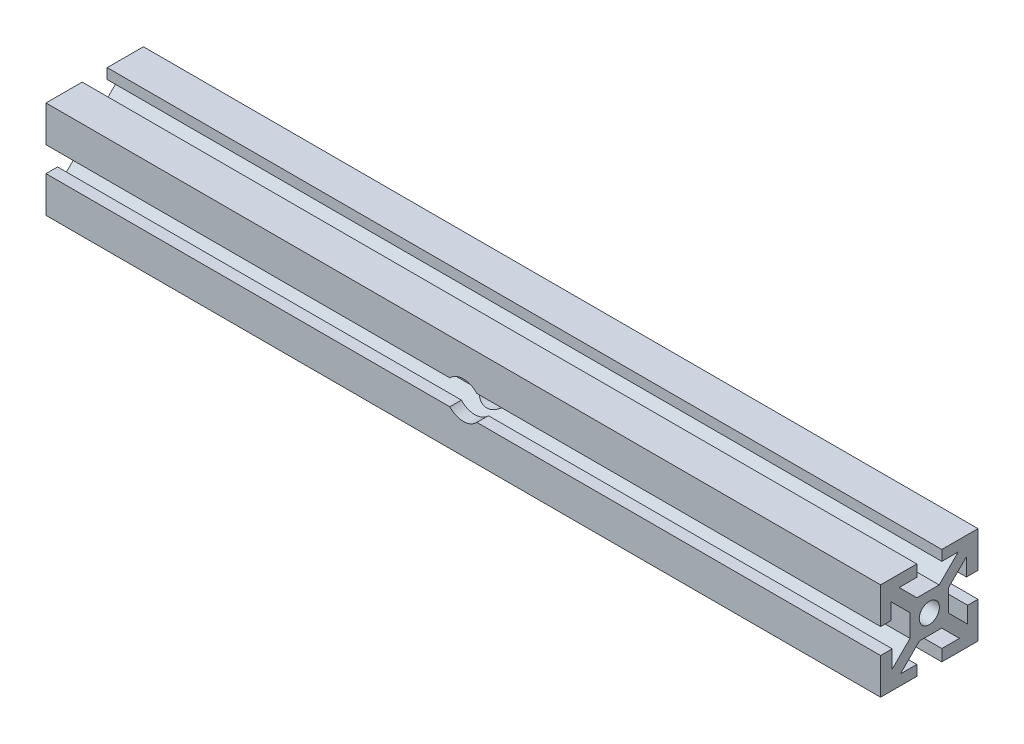
SolidWorks part; units mm, degrees
material "6061 Alloy"
ref_plane "Front Plane" through (0, 0, 0) normal (0, 0, 1) x (1, 0, 0)
ref_plane "Top Plane" through (0, 0, 0) normal (0, 1, 0) x (1, 0, 0)
ref_plane "Right Plane" through (0, 0, 0) normal (1, 0, 0) x (0, 0, -1)
sketch "Sketch1" plane through (0, 0, 0) normal (1, 0, 0) x (0, 0, -1)
  line L0 (2.5534, 5) -> (7.4749, 9.9215)
  line L1 (-5, 5) -> (5, 5)
  line L2 (-5, 5) -> (-5, -5)
  line L3 (-5, -5) -> (5, -5)
  line L4 (5, 5) -> (5, -5)
  line L5 (-5, 5) -> (5, -5) construction
  line L6 (-5, -5) -> (5, 5) construction
  line L7 (7.4749, 9.9215) -> (9.5962, 7.8001)
  line L8 (9.5962, 7.8001) -> (5, 3.2039)
  line L9 (5, 5) -> (13.6489, 13.6489) construction
  line L10 (7.4749, 9.9215) -> (3.24, 9.9215)
  line L11 (3.24, 9.9215) -> (3.24, 12.5962)
  line L12 (3.24, 12.5962) -> (12.5962, 12.5962)
  line L13 (9.5962, 7.8001) -> (9.5962, 3.24)
  line L14 (9.5962, 3.24) -> (12.5962, 3.24)
  line L15 (12.5962, 3.24) -> (12.5962, 12.5962)
  line L17 (0, 0) -> (0, 24.089) construction
  line L18 (0, 0) -> (23.75, 0) construction
  circle A0 centre (0, 0) radius 2.605
  point P0 (0, 0)
  dimension "D1" = 5.21
  dimension "D2" = 10
  dimension "D3" = 10
  dimension "D4" = 3
  dimension "D5" = 1.27
  dimension "D6" = 6.5
  dimension "D7" = 3.24
  dimension "D8" = 3.24
  dimension "D9" = 3
extrude "Boss-Extrude1" add sketch "Sketch1" along normal blind 215.9 contours L4 L1 L2 L3 A0 | L8 L7 L0 L1 L4 | L14 L15 L12 L11 L10 L7 L13 region at (0, 4.8586, -3.7767) region at (0, 6.7479, -6.3823) region at (0, 9.18, -9.3105)
ref_axis "Axis1" through (0, 0, 0) along (1, 0, 0)
pattern_circular "CirPattern1" count 4 over 360 about axis through (0, 0, 0) along (1, 0, 0) of "Boss-Extrude1"
sketch "Sketch2" plane through (0, 0, 12.5962) normal (0, 0, 1) x (1, 0, 0)
  line L0 (0, -9.5962) -> (0, -5) construction
  circle A0 centre (107.95, 0) radius 4.765
  point P2 (0, -7.2981)
  dimension "D1" = 9.53
  dimension "D2" = 107.95
extrude "Cut-Extrude2" cut sketch "Sketch2" against normal blind 50 and the other way blind 10
